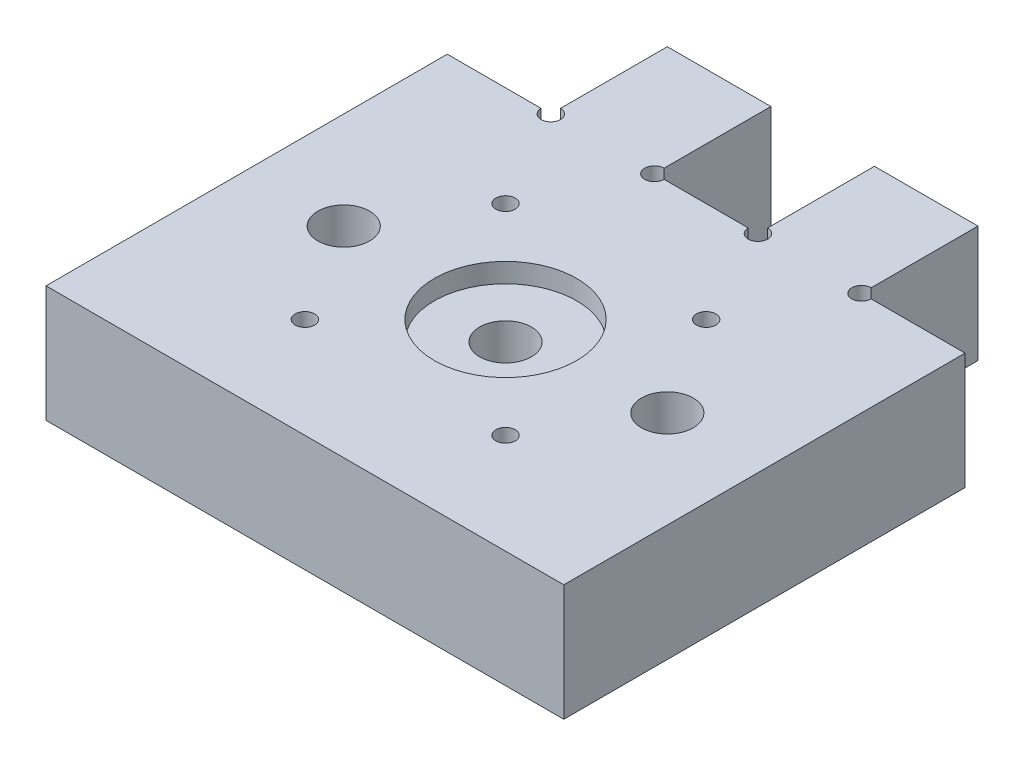
SolidWorks part; units mm, degrees
ref_plane "Front Plane" through (0, 0, 0) normal (0, 0, 1) x (1, 0, 0)
ref_plane "Top Plane" through (0, 0, 0) normal (0, 1, 0) x (1, 0, 0)
ref_plane "Right Plane" through (0, 0, 0) normal (1, 0, 0) x (0, 0, -1)
sketch "Sketch1" plane through (0, 0, 0) normal (0, 1, 0) x (1, 0, 0)
  line L0 (-1000, 0) -> (49000, 0) construction
  line L5 (0, -1000) -> (0, 49000) construction
  line L6 (-40, 31) -> (-24, 31)
  line L7 (-40, -31) -> (40, -31)
  line L8 (-40, -31) -> (-40, 31)
  line L9 (-24, 49) -> (-8, 49)
  line L10 (40, -31) -> (40, 31)
  line L11 (-24, 49) -> (-24, 31)
  line L12 (-8, 49) -> (-8, 31)
  line L13 (8, 49) -> (8, 31)
  line L14 (24, 49) -> (24, 31)
  line L16 (24, 31) -> (40, 31)
  line L17 (8, 49) -> (24, 49)
  line L18 (-8, 31) -> (8, 31)
  circle A10 centre (0, 0) radius 4
  circle A11 centre (15.5, 15.5) radius 1.5
  circle A12 centre (-15.5, 15.5) radius 1.5
  circle A13 centre (-15.5, -15.5) radius 1.5
  circle A14 centre (15.5, -15.5) radius 1.5
  circle A15 centre (25, 0) radius 4
  circle A16 centre (-25, 0) radius 4
  point P6 (0, 31)
  point P10 (-40, 0)
  dimension "D3" = 8
  dimension "D4" = 15.5
  dimension "D6" = 3
  dimension "D12" = 8
  dimension "D2" = 80
  dimension "D5" = 15.5
  dimension "D7" = 18
  dimension "D9" = 4
  dimension "D8" = 16
  dimension "D10" = 16
  dimension "D11" = 80
  dimension "D13" = 25
extrude "Boss-Extrude1" add sketch "Sketch1" along normal blind 18
sketch "Sketch2" plane through (0, 18, 0) normal (0, 1, 0) x (1, 0, 0)
  circle A0 centre (0, 0) radius 11
  dimension "D1" = 22
extrude "Cut-Extrude1" cut sketch "Sketch2" against normal blind 3
sketch "Sketch3" plane through (0, 18, 0) normal (0, 1, 0) x (1, 0, 0)
  circle A0 centre (-24, 31) radius 1.5
  circle A1 centre (-8, 31) radius 1.5
  circle A2 centre (8, 31) radius 1.5
  circle A3 centre (24, 31) radius 1.5
  dimension "D1" = 3
  dimension "D3" = 16
  dimension "D2" = 4
extrude "Cut-Extrude2" cut sketch "Sketch3" against normal through all
